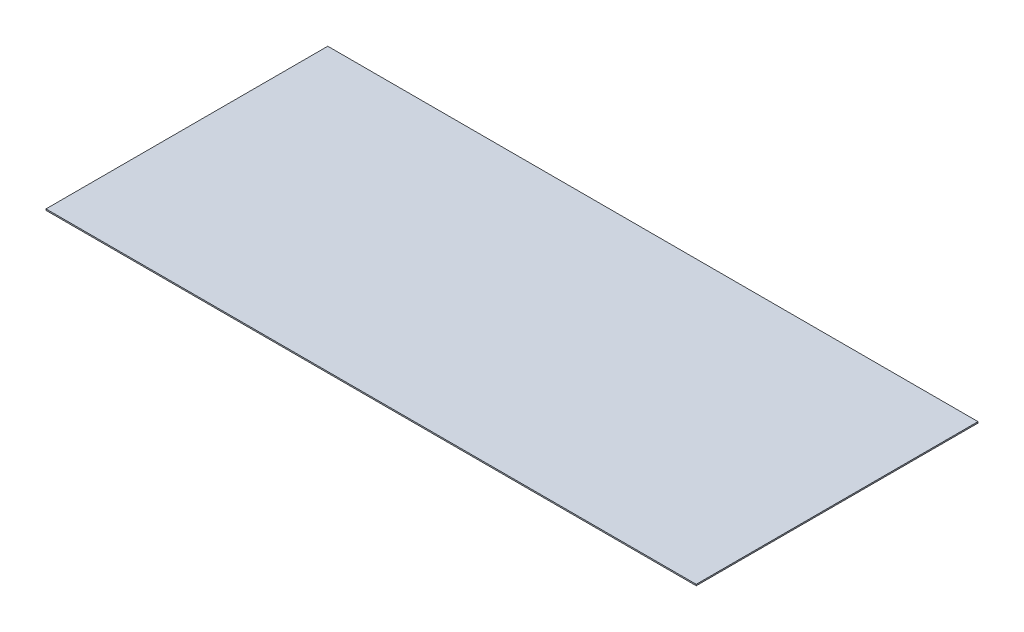
SolidWorks part; units mm, degrees
material "AISI 304"
ref_plane "Front Plane" through (0, 0, 0) normal (0, 0, 1) x (1, 0, 0)
ref_plane "Top Plane" through (0, 0, 0) normal (0, 1, 0) x (1, 0, 0)
ref_plane "Right Plane" through (0, 0, 0) normal (1, 0, 0) x (0, 0, -1)
sketch "Sketch1" plane through (0, 0, 0) normal (0, 1, 0) x (1, 0, 0)
  line L1 (300, -130) -> (-300, -130)
  line L2 (300, -130) -> (300, 130)
  line L3 (300, 130) -> (-300, 130)
  line L4 (-300, -130) -> (-300, 130)
  line L5 (300, -130) -> (-300, 130) construction
  line L6 (300, 130) -> (-300, -130) construction
  point P0 (0, 0)
  dimension "D1" = 260
  dimension "D2" = 600
base flange "Base-Flange1" sketch "Sketch1" thickness 1.2 reverse thickness direction no parameters "D1"=0.7366
sketch "Bend-Lines1" [suppressed] plane through (0, 0, 0) normal (0, 1, 0) x (1, 0, 0)
sketch "Bounding-Box1" [suppressed] plane through (0, 0, 0) normal (0, 1, 0) x (1, 0, 0)
sheet metal parameters "Sheet-Metal1" thickness 1.2 parameters "D1"=0.7366
flat pattern "Flat-Pattern1" [suppressed]
sketch "Bend-Lines2" plane through (0, 0, 0) normal (0, 1, 0) x (1, 0, 0)
sketch3d "Bounding-Box2" [suppressed]
  line L0 (-300, -130, 0) -> (300, -130, 0) construction
  line L1 (-300, 130, 0) -> (300, 130, 0) construction
  line L2 (-300, -130, 0) -> (-300, 130, 0) construction
  line L3 (300, -130, 0) -> (300, 130, 0) construction
